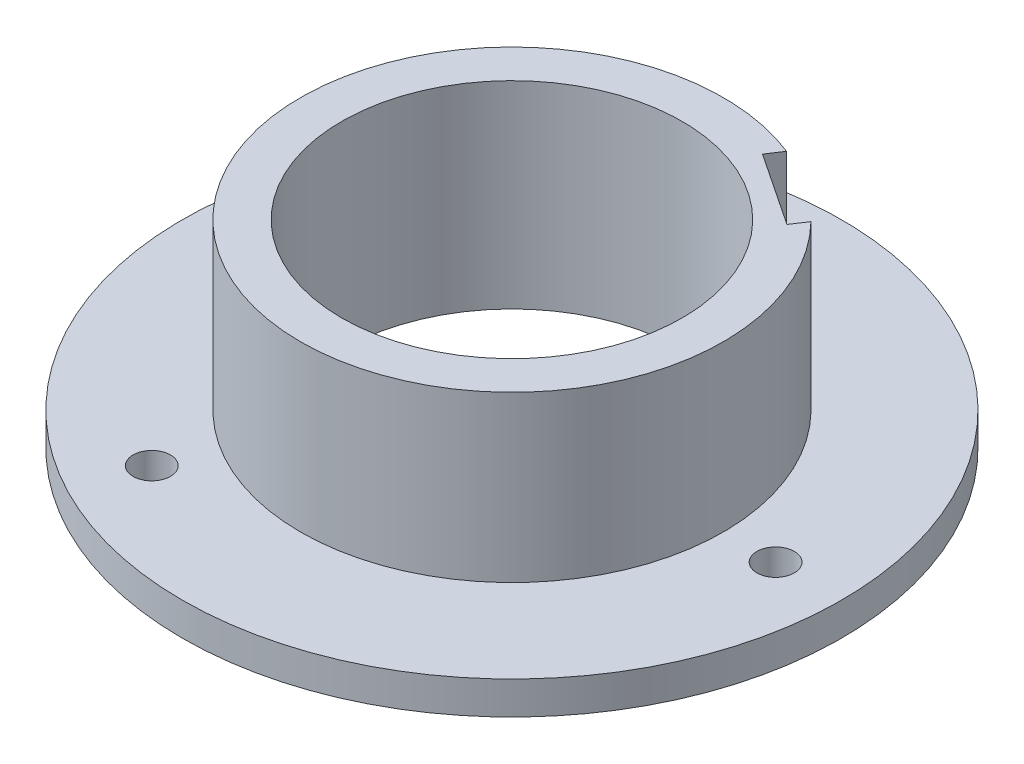
SolidWorks part; units mm, degrees
material "PETG"
ref_plane "Front Plane" through (0, 0, 0) normal (0, 0, 1) x (1, 0, 0)
ref_plane "Top Plane" through (0, 0, 0) normal (0, 1, 0) x (1, 0, 0)
ref_plane "Right Plane" through (0, 0, 0) normal (1, 0, 0) x (0, 0, -1)
sketch "Sketch2" plane through (0, 0, 0) normal (0, 1, 0) x (1, 0, 0)
  circle A0 centre (0, 0) radius 30
  circle A1 centre (0, 0) radius 15.5
  circle A2 centre (0, 0) radius 19.25
  dimension "D1" = 60
  dimension "D2" = 31
  dimension "D3" = 38.5
extrude "flang" add sketch "Sketch2" along normal blind 3 contours A0 A2 region at (-29.1515, 0, 0)
extrude "skirt" add sketch "Sketch2<3>" along normal blind 18 contours A2 A1 region at (-18.7055, 0, 0)
sketch "Sketch2<3>" plane through (0, 0, 0) normal (0, 1, 0) x (1, 0, 0) same geometry as "Sketch2"
sketch "Sketch3" plane through (0, 3, 0) normal (0, 1, 0) x (1, 0, 0)
  circle A0 centre (0, 0) radius 24 construction
  circle A5 centre (0, 0) radius 24 construction
  circle A7 centre (0, 0) radius 24 construction
  circle A8 centre (24, 0) radius 1.7
  circle A9 centre (-12, -20.7846) radius 1.7
  circle A10 centre (0, 0) radius 24 construction
  circle A11 centre (-12, 20.7846) radius 1.7
  circle A12 centre (0, 0) radius 24 construction
  point P13 (0, 0)
  point P16 (0, 0)
  dimension "D1" = 48
  dimension "D2" = 3.4
  dimension "D3" = 3
  dimension "D4" = 3
extrude "holes_bolts" cut sketch "Sketch3" against normal through all
sketch "Sketch8" plane through (0, 3, 0) normal (0, 1, 0) x (1, 0, 0)
  line L4 (0, 0) -> (41.5762, 62.4213) construction
  line L5 (14.0004, 13.8041) -> (7.3421, 18.2389)
  line L6 (7.3421, 18.2389) -> (6.2334, 16.5743)
  line L7 (6.2334, 16.5743) -> (12.8917, 12.1395)
  line L8 (12.8917, 12.1395) -> (14.0004, 13.8041)
  circle A0 centre (0, 0) radius 19.25 construction
  circle A2 centre (0, 0) radius 75 construction
  point P11 (10.6712, 16.0215)
  dimension "D1" = 8
  dimension "D2" = 2
extrude "service_slot" cut sketch "Sketch8" along normal through all
equation "\"____ GENERATED PART EXPORTS ____\" = 0"
equation "\"SYS_VersionTag\" = 2"
equation "\"LDG_Enabled\" = 1"
equation "\"LDG_IsStructural\" = 0"
equation "\"LDG_FlangeThk\" = 3mm"
equation "\"LDG_MountBCDia\" = 48mm"
equation "\"LDG_MountClearDia\" = 3.4mm"
equation "\"LDG_MountCount\" = 3"
equation "\"LDG_ID\" = 31mm"
equation "\"LDG_WallThk\" = 3.75mm"
equation "\"LDG_OD\" = 38.5mm"
equation "\"LDG_SkirtLength\" = 18mm"
equation "\"LDG_ServiceSlotWidth\" = 8mm"
equation "\"LDG_ServiceSlotSectorDeg\" = 225"
equation "\"D2@Sketch2\"=\"LDG_ID\""
equation "\"D3@Sketch2\"=\"LDG_OD\""
equation "\"D1@flang\" = \"LDG_FlangeThk\""
equation "\"D1@skirt\" = \"LDG_SkirtLength\""
equation "\"D1@Sketch3\"=\"LDG_MountBCDia\""
equation "\"D2@Sketch3\"=\"LDG_MountClearDia\""
equation "\"D1@Sketch8\"=\"LDG_ServiceSlotWidth\""
